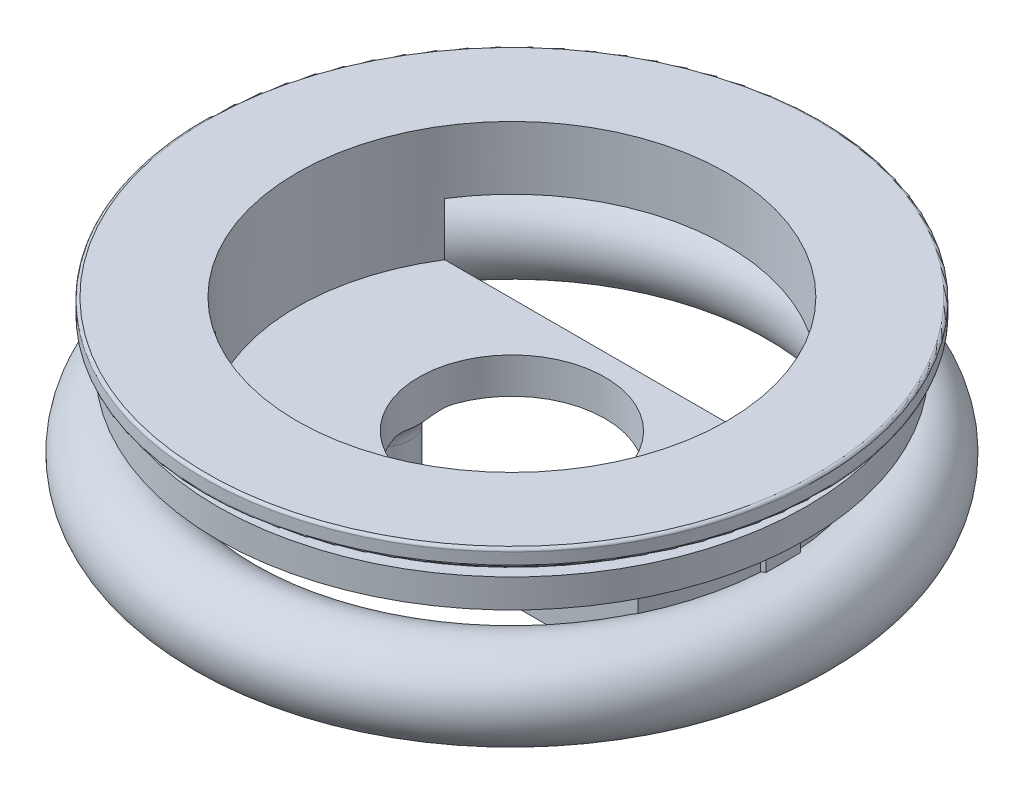
SolidWorks part; units mm, degrees
ref_plane "Front Plane" through (0, 0, 0) normal (0, 0, 1) x (1, 0, 0)
ref_plane "Top Plane" through (0, 0, 0) normal (0, 1, 0) x (1, 0, 0)
ref_plane "Right Plane" through (0, 0, 0) normal (1, 0, 0) x (0, 0, -1)
sketch "Sketch1" plane through (0, 0, 0) normal (0, 0, 1) x (1, 0, 0)
  line L0 (8.7584, 11.2) -> (0, 11.2)
  line L1 (0, 11.2) -> (0, 5.9)
  line L2 (9.2986, 9) -> (9.2986, 5.9)
  line L3 (9.2986, 5.9) -> (0, 5.9)
  line L5 (10.7584, 11.2) -> (10.7584, 10.6)
  line L6 (8.7584, 11.2) -> (10.7584, 11.2)
  line L7 (10.7584, 10.6) -> (9.8584, 10.6)
  line L8 (10.2708, 9) -> (9.2986, 9)
  line L9 (-0.766, 5.9) -> (-0.1737, 5.9) construction
  line L10 (0, 0) -> (0, -5.523) construction
  line L11 (9.8584, 10.6) -> (9.8584, 10)
  line L12 (9.8584, 10) -> (10.2708, 10)
  line L13 (10.2708, 10) -> (10.2708, 9)
  dimension "D3" = 0.6
  dimension "D4" = 0.6
  dimension "D5" = 9.8584
  dimension "D7" = 9
  dimension "D8" = 1
  dimension "D9" = 2
  dimension "D10" = 8.7584
revolve "Revolve1" add sketch "Sketch1" angle 360 about L10
sketch "Sketch11" plane through (0, 11.2, 0) normal (0, 1, 0) x (1, 0, 0)
  circle A0 centre (0, 0) radius 7.5
  dimension "D1" = 15
extrude "Cut-Extrude5" cut sketch "Sketch11" against normal offset from surface (4.05 mm away) 1.25 up to face at (0, 5.9, 9.2986)
sketch "Sketch21" plane through (0, 0, 0) normal (1, 0, 0) x (0, 0, -1)
  line L1 (-1.28, 6.2) -> (-0.98, 6.2)
  line L2 (-1.28, 6.2) -> (-1.28, 5.9)
  line L3 (-1.28, 5.9) -> (-0.98, 5.9)
  line L4 (-0.98, 6.2) -> (-0.98, 5.9)
ref_axis "Axis2" through (0, 5.9, 0) along (0, 1, 0)
revolve "Cut-Revolve3" cut sketch "Sketch21" angle 30 about axis through (0, 5.9, 0) along (0, 1, 0)
sketch "Sketch3" plane through (0, 0, 0) normal (1, 0, 0) x (0, 0, -1)
  line L1 (10.2708, 9) -> (4, 9)
  line L2 (10.2708, 9) -> (10.2708, 1.577)
  line L3 (10.2708, 1.577) -> (4, 1.577)
  line L4 (4, 9) -> (4, 1.577)
  dimension "D1" = 4
extrude "Cut-Extrude2" cut sketch "Sketch3" against normal through all and the other way through all
mirror "Mirror1" about plane through (0, 0, 0) normal (0, 0, 1) of "Cut-Extrude2"
sketch "Sketch23" plane through (0, 5.9, 0) normal (0, -1, 0) x (1, 0, 0)
  line L0 (4.545, 0) -> (0, 0) construction
  line L1 (0, 0) -> (-4.545, 0) construction
  circle A0 centre (4.545, 0) radius 1
  circle A1 centre (-4.545, 0) radius 1
  dimension "D2" = 2
  dimension "D3" = 2
  dimension "D1" = 9.09
extrude "Boss-Extrude6" add sketch "Sketch23" along normal blind 5
fillet "Fillet15" radius 0.8 2 edges at (4.545, 0.9, -1) (-4.545, 0.9, -1)
sketch "Sketch7" plane through (0, 0, 0) normal (0, 0, -1) x (-1, 0, 0)
  line L0 (9.4703, 9.2337) -> (9.4703, 4.6032)
  line L1 (9.4703, 4.6032) -> (4.5936, 2.3839)
  line L2 (4.5936, 2.3839) -> (4.5936, 5.6514)
  line L4 (4.5936, 5.6514) -> (7.3393, 6.7383)
  line L5 (8.8342, 9.2337) -> (9.4703, 9.2337)
  line L6 (7.3393, 6.7383) -> (8.8342, 9.2337)
extrude "Boss-Extrude3" add sketch "Sketch7" along normal blind 0.6 and the other way blind 0.6
pattern_circular "CirPattern2" count 2 over 360 about axis through (0, 0, 0) along (0, 1, 0) of "Boss-Extrude3"
fillet "Fillet5" radius 3 2 edges at (9.4703, 4.6032, 0) (-9.4703, 4.6032, 0)
fillet "Fillet6" radius 0.1 2 edges at (0, 11.2, 10.7584) (0, 10.6, 10.7584)
sketch "Sketch8" plane through (0, 0, 0) normal (1, 0, 0) x (0, 0, -1)
  line L0 (0, 0) -> (0, 15.0321) construction
  circle A0 centre (10, 6.5) radius 1.5
  dimension "D3" = 3
  dimension "D1" = 6.5
  dimension "D2" = 10
revolve "Revolve2" add sketch "Sketch8" angle 360 about L0
fillet "Fillet16" radius 0.8 6 edges at (6.9747, 5.9, 0.6) (3.545, 5.9, 0) (6.9747, 5.9, -0.6) (-6.9747, 5.9, -0.6) (-6.9747, 5.9, 0.6) (-3.545, 5.9, 0)
fillet "Fillet17" radius 0.5 2 edges at (-5.545, 2.8168, 0) (5.545, 2.8168, 0)
sketch "Sketch24" plane through (0, 7.15, 0) normal (0, 1, 0) x (1, 0, 0)
  circle A0 centre (0, 0) radius 3.25
  dimension "D1" = 6.5
extrude "Cut-Extrude7" cut sketch "Sketch24" against normal through all contours A0
